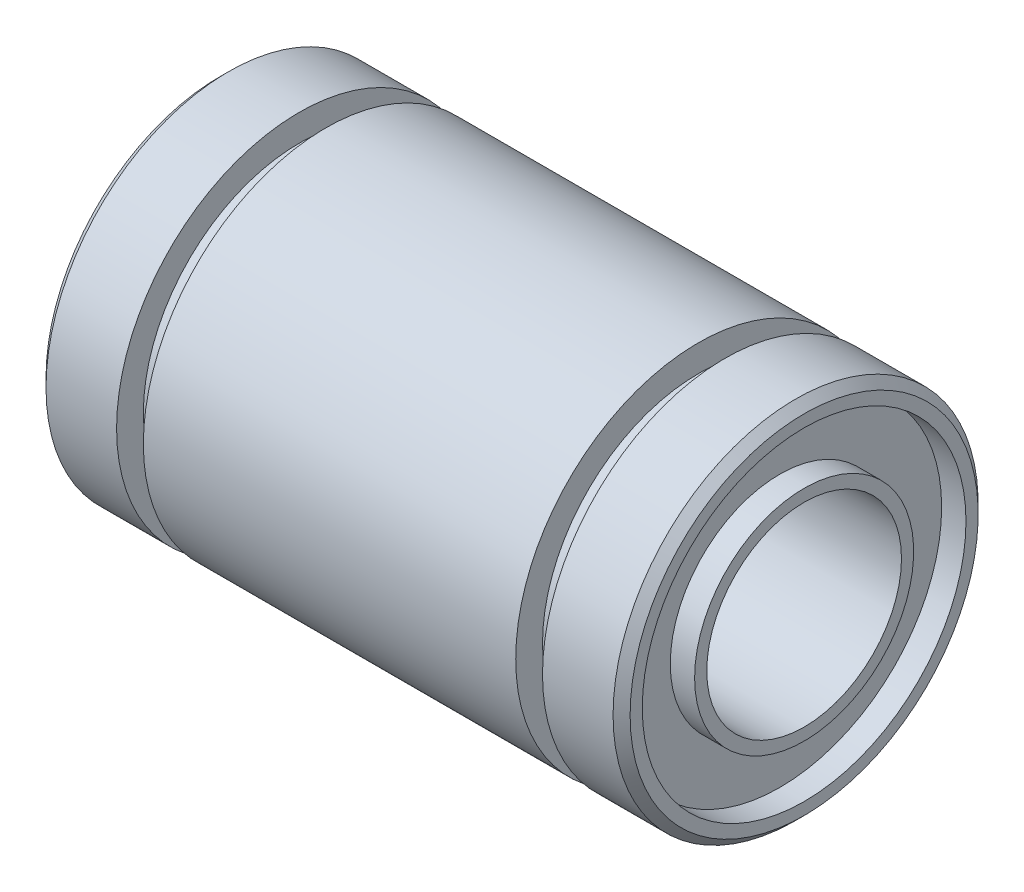
SolidWorks part; units mm, degrees
material "1060 Alloy"
ref_plane "Front Plane" through (0, 0, 0) normal (0, 0, 1) x (1, 0, 0)
ref_plane "Top Plane" through (0, 0, 0) normal (0, 1, 0) x (1, 0, 0)
ref_plane "Right Plane" through (0, 0, 0) normal (1, 0, 0) x (0, 0, -1)
sketch "Sketch1" plane through (0, 0, 0) normal (0, 0, 1) x (1, 0, 0)
  line L0 (-45.6895, 0) -> (45.6895, 0) construction
  line L1 (-11.65, 7.5) -> (-8.75, 7.5)
  line L2 (-8.75, 7.5) -> (-8.75, 6.4)
  line L3 (-8.75, 6.4) -> (-7.65, 6.4)
  line L4 (-7.65, 6.4) -> (-7.65, 7.5)
  line L5 (-7.65, 7.5) -> (7.65, 7.5)
  line L6 (0, 45.6895) -> (0, -45.6895) construction
  line L7 (-11.65, 7.5) -> (-12, 7.15)
  line L8 (-12, 7.15) -> (-12, 6.65)
  line L9 (-12, 6.65) -> (-11, 6.65)
  line L10 (-11, 6.65) -> (-11, 4.5)
  line L11 (-11, 4.5) -> (-12, 4.5)
  line L12 (-12, 4.5) -> (-12, 4)
  line L13 (-12, 4) -> (12, 4)
  line L14 (12, 4.5) -> (12, 4)
  line L15 (11, 4.5) -> (12, 4.5)
  line L16 (11, 6.65) -> (11, 4.5)
  line L17 (12, 6.65) -> (11, 6.65)
  line L18 (12, 7.15) -> (12, 6.65)
  line L19 (11.65, 7.5) -> (12, 7.15)
  line L20 (7.65, 6.4) -> (7.65, 7.5)
  line L21 (8.75, 6.4) -> (7.65, 6.4)
  line L22 (8.75, 7.5) -> (8.75, 6.4)
  line L23 (11.65, 7.5) -> (8.75, 7.5)
  point P19 (0, 4)
  point P26 (0, 7.5)
  dimension "D1" = 45
  dimension "D2" = 1.1
  dimension "D3" = 0.5
  dimension "L" = 24
  dimension "B" = 17.5
  dimension "W" = 1.1
  dimension "D" = 7.5
  dimension "D_1" = 7.15
  dimension "D4" = 0.5
  dimension "dr" = 4
  dimension "D5" = 1
revolve "Revolve1" add sketch "Sketch1" angle 360 about L0 region at (0, 5.7195, 0)
equation "\"D\"=15"
equation "\"D1\"=14.3"
equation "\"dr\"=8"
equation "\"L\"=24"
equation "\"B\"=17.5"
equation "\"W\"=1.1"
equation "\"L@Sketch1\"= \"L\""
equation "\"B@Sketch1\"= \"B\""
equation "\"W@Sketch1\"= \"W\""
equation "\"dr@Sketch1\"= \"dr\" * 0.5"
equation "\"D@Sketch1\" = \"D\" * 0.5"
equation "\"D_1@Sketch1\" = \"D1\" * 0.5"
